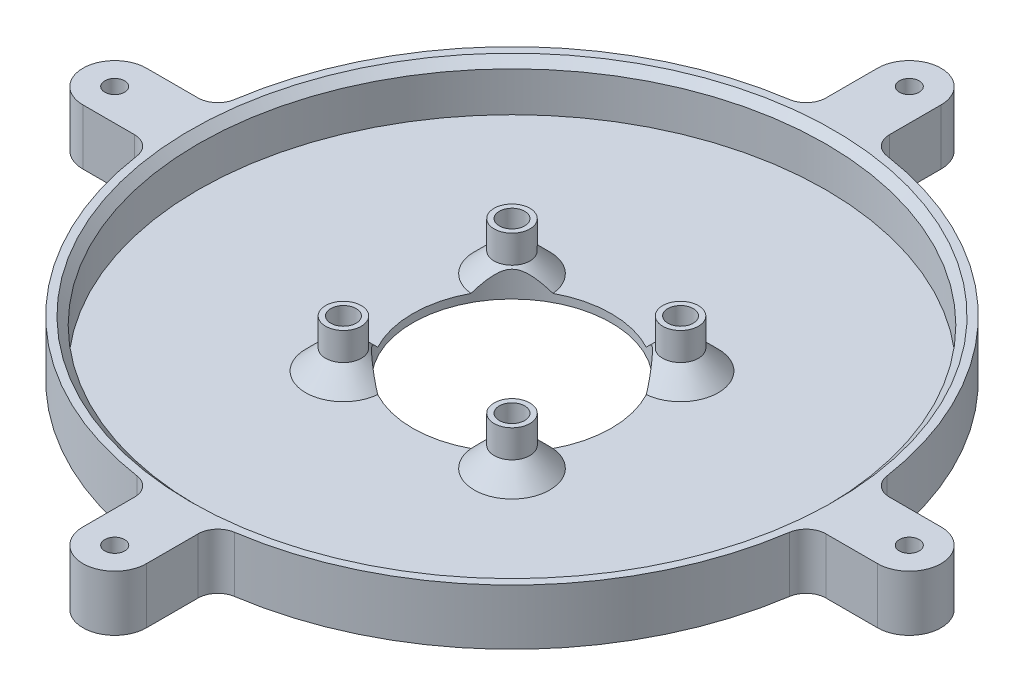
SolidWorks part; units mm, degrees
material "6061-T6 (SS)"
ref_plane "Front" through (0, 0, 0) normal (0, 0, 1) x (1, 0, 0)
ref_plane "Top" through (0, 0, 0) normal (0, 1, 0) x (1, 0, 0)
ref_plane "Right" through (0, 0, 0) normal (1, 0, 0) x (0, 0, -1)
sketch "Sketch1" plane through (0, 0, 0) normal (0, 1, 0) x (1, 0, 0)
  line L0 (0, 0) -> (0, 50) construction
  line L1 (0, 0) -> (0, -50) construction
  line L2 (0, 0) -> (50, 0) construction
  line L3 (0, 0) -> (-50, 0) construction
  line L4 (0, 50) -> (0, -50) construction
  line L5 (4, 50) -> (4, -50)
  line L6 (-4, 50) -> (-4, -50)
  line L7 (-50, 0) -> (50, 0) construction
  line L8 (-50, 4) -> (50, 4)
  line L9 (-50, -4) -> (50, -4)
  circle A0 centre (0, 0) radius 41.5
  arc A2 (4, 50) -> (-4, 50) centre (0, 50) ccw
  arc A3 (-4, -50) -> (4, -50) centre (0, -50) ccw
  arc A4 (-50, 4) -> (-50, -4) centre (-50, 0) ccw
  arc A5 (50, -4) -> (50, 4) centre (50, 0) ccw
  point P3 (0, 0)
  point P12 (0, 0)
  dimension "D1" = 83
  dimension "D3" = 4
  dimension "D4" = 4
  dimension "D2" = 50
extrude "Boss-Extrude1" add sketch "Sketch1" along normal blind 7 contours L5 A2 L6 A0 | L9 A5 L8 A0 | L8 A4 L9 A0 | L6 A3 L5 A0 | L5 A0 L9 | L8 A0 L5 | L6 A0 L8 | L9 A0 L6 | L9 A0 L8 L5 | L5 A0 L6 L8 | L8 A0 L9 L6 | L6 A0 L5 L9 | L6 L9 L5 L8 region at (0, 0, -47.3225) region at (19.3714, 0, -19.3714) region at (0, 0, -22.7179) region at (22.7179, 0, 0) region at (0, 0, 0) region at (47.3225, 0, 0) region at (-19.3714, 0, -19.3714) region at (19.3714, 0, 19.3714) region at (0, 0, 22.7179) region at (-22.7179, 0, 0) region at (-47.3225, 0, 0) region at (0, 0, 47.3225) region at (-19.3714, 0, 19.3714)
sketch "Sketch3" plane through (0, 7, 0) normal (0, 1, 0) x (1, 0, 0)
  circle A0 centre (0, 0) radius 39.5
  arc A1 (41.3068, 4) -> (4, 41.3068) centre (0, 0) ccw construction
  dimension "D1" = 2
extrude "Cut-Extrude1" cut sketch "Sketch3" against normal offset from surface (6 mm away) 1 up to face at (0, 0, 0)
sketch "Sketch5" plane through (0, 1, 0) normal (0, 1, 0) x (1, 0, 0)
  line L0 (-10.6066, -10.6066) -> (10.6066, 10.6066) construction
  line L1 (-10.6066, 10.6066) -> (10.6066, -10.6066) construction
  line L2 (0, 0) -> (21.2594, 0) construction
  circle A0 centre (-10.6066, 10.6066) radius 2.25
  circle A1 centre (-10.6066, 10.6066) radius 1.6
  point P4 (0, 0)
  point P7 (0, 0)
  dimension "D4" = 4.5
  dimension "D5" = 3.2
  dimension "D1" = 45
  dimension "D2" = 45
  dimension "D3" = 30
extrude "Boss-Extrude2" add sketch "Sketch5" along normal up to surface (6 mm away) up to face at (0, 7, 39.5)
chamfer "Chamfer1" distance 2.5 angle 45 1 edges at (-10.6066, 1, -8.3566)
pattern_circular "CirPattern1" count 4 over 360 about axis through (0, 7, 0) along (0, 1, 0) of "Chamfer1", "Boss-Extrude2"
sketch "Sketch4" plane through (0, 1, 0) normal (0, 1, 0) x (1, 0, 0)
  circle A0 centre (0, 0) radius 12.5
  dimension "D1" = 25
extrude "Cut-Extrude2" cut sketch "Sketch4" against normal through all both and the other way through all
hole_wizard "M3x0.5 Tapped Hole1" positions "Sketch6" profile "Sketch7" tap size "M3x0.5" standard "ANSI Metric" end condition through all
sketch "Sketch6" plane through (0, 7, 0) normal (0, 1, 0) x (1, 0, 0)
  point P2 (0, 50)
  point P5 (50, 0)
  point P8 (-50, 0)
  point P11 (0, -50)
sketch "Sketch7" plane through (0, 7, -50) normal (1, 0, 0) x (0, 0, 1)
  line L0 (0, 0) -> (0, 7)
  line L1 (0, 7) -> (1.25, 7)
  line L2 (1.25, 7) -> (1.25, 0)
  line L5 (1.25, 0) -> (0, 0)
  line L11 (0, -6.35) -> (0, 107.95) construction
  dimension "Thru Tap Drill Dia." = 2.5
  dimension "Thru Tap Drill Depth" = 7
cosmetic thread "Hole Thread1" parameters "D2"=3
cosmetic thread "Hole Thread2" parameters "D2"=3
cosmetic thread "Hole Thread3" parameters "D2"=3
cosmetic thread "Hole Thread4" parameters "D2"=3
chamfer "Chamfer2" distance 1 1 edges at (0, 7, 39.5)
fillet "Fillet1" radius 2.5 8 edges at (-41.3068, 3.5, -4) (-4, 3.5, -41.3068) (4, 3.5, -41.3068) (41.3068, 3.5, -4) (41.3068, 3.5, 4) (4, 3.5, 41.3068) (-4, 3.5, 41.3068) (-41.3068, 3.5, 4)
sketch "Sketch8" plane through (0, 1, 0) normal (0, 1, 0) x (1, 0, 0)
  circle A0 centre (-10.6066, 10.6066) radius 1.6 construction
  circle A1 centre (10.6066, 10.6066) radius 1.6
  circle A2 centre (10.6066, 10.6066) radius 1.6
  circle A3 centre (-10.6066, -10.6066) radius 1.6 construction
  circle A4 centre (10.6066, -10.6066) radius 1.6 construction
  circle A5 centre (-10.6066, 10.6066) radius 1.6
  circle A6 centre (-10.6066, -10.6066) radius 1.6
  circle A7 centre (10.6066, -10.6066) radius 1.6
  dimension "D1" = 0
extrude "Cut-Extrude3" cut sketch "Sketch8" against normal through all
equation "\"D4@Sketch1\"=\"D3@Sketch1\""
